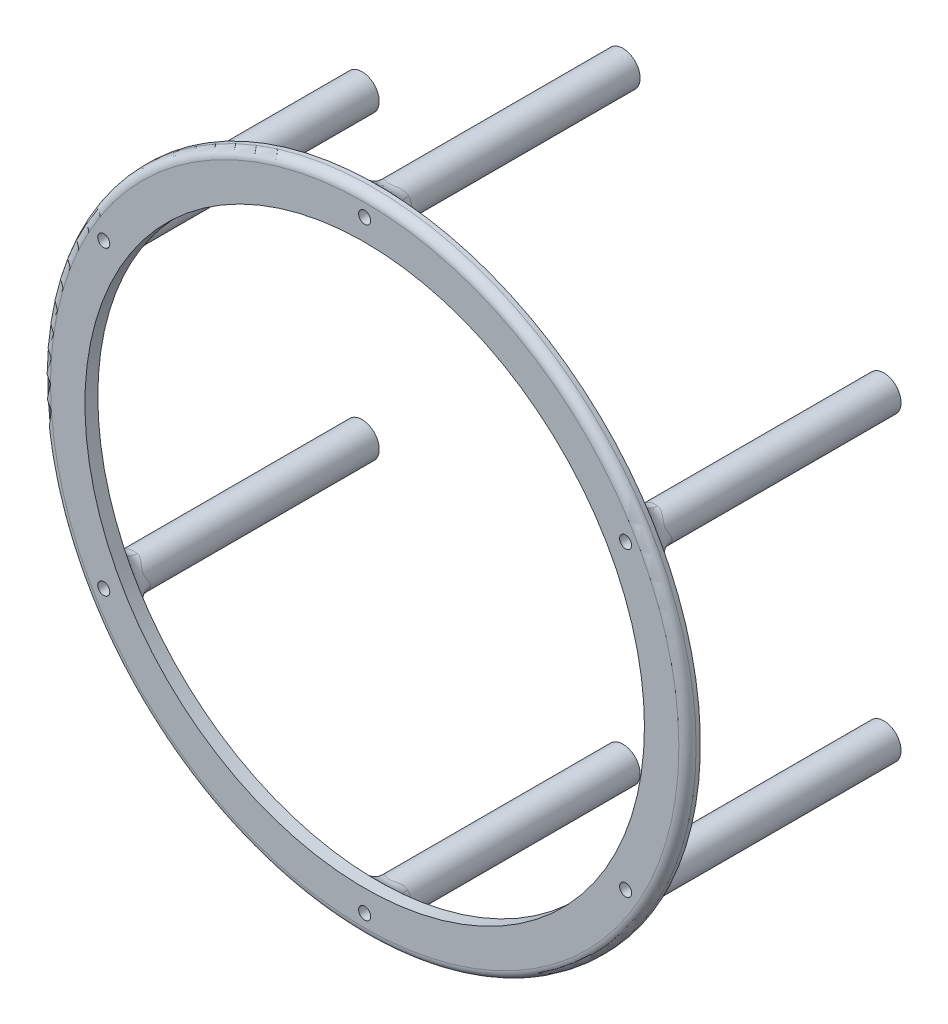
SolidWorks part; units mm, degrees
material "ABS"
ref_plane "正面" through (0, 0, 0) normal (0, 0, 1) x (1, 0, 0)
ref_plane "平面" through (0, 0, 0) normal (0, 1, 0) x (1, 0, 0)
ref_plane "右側面" through (0, 0, 0) normal (1, 0, 0) x (0, 0, -1)
sketch "ｽｹｯﾁ1" plane through (0, 0, 0) normal (0, 0, 1) x (1, 0, 0)
  circle A0 centre (0, 0) radius 65
  circle A1 centre (0, 0) radius 75
  circle A2 centre (0, 0) radius 70 construction
  circle A3 centre (0, 70) radius 1.4
  circle A4 centre (60.6218, 35) radius 1.4
  circle A5 centre (60.6218, -35) radius 1.4
  circle A6 centre (0, -70) radius 1.4
  circle A7 centre (-60.6218, -35) radius 1.4
  circle A8 centre (-60.6218, 35) radius 1.4
  point P19 (0, 0)
  dimension "D1" = 140
  dimension "D2" = 130
  dimension "D3" = 150
  dimension "D4" = 2.8
  dimension "D5" = 6
extrude "ﾎﾞｽ - 押し出し1" add sketch "ｽｹｯﾁ1" along normal blind 3
fillet "ﾌｨﾚｯﾄ1" radius 2 1 edges at (75, 0, 3)
sketch "ｽｹｯﾁ2" plane through (0, 0, 0) normal (0, 0, -1) x (-1, 0, 0)
  circle A0 centre (0, 70) radius 4
  circle A1 centre (0, 70) radius 1.4 construction
  circle A2 centre (0, 70) radius 1.4
  dimension "D1" = 8
extrude "ﾎﾞｽ - 押し出し2" add sketch "ｽｹｯﾁ2" along normal blind 57
sketch "ｽｹｯﾁ3" plane through (0, 0, 0) normal (0, 1, 0) x (1, 0, 0)
  line L0 (0, 0) -> (0, 45.2792)
pattern_circular "円形ﾊﾟﾀｰﾝ1" count 6 over 360 about axis through (0, 0, 0) along (0, 0, -1) of "ﾎﾞｽ - 押し出し2" reverse direction yes
fillet "ﾌｨﾚｯﾄ2" radius 4 6 edges at (-56.6218, -35, 0) (4, -70, 0) (64.6218, -35, 0) (64.6218, 35, 0) (4, 70, 0) (-56.6218, 35, 0)
